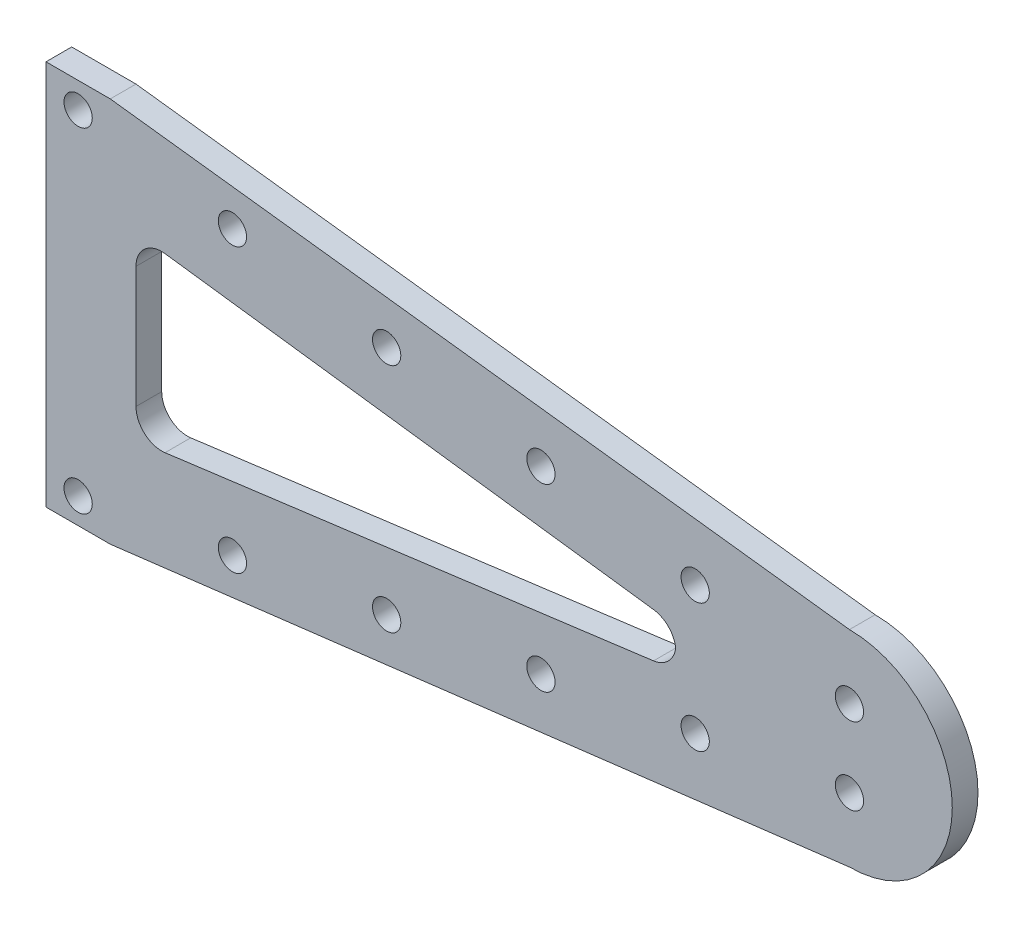
SolidWorks part; units mm, degrees
ref_plane "前基準面" through (0, 0, 0) normal (0, 0, 1) x (1, 0, 0)
ref_plane "上基準面" through (0, 0, 0) normal (0, 1, 0) x (1, 0, 0)
ref_plane "右基準面" through (0, 0, 0) normal (1, 0, 0) x (0, 0, -1)
sketch "草圖1" plane through (0, 0, 0) normal (0, 0, 1) x (1, 0, 0)
  line L0 (2.5, 15) -> (60, 8)
  line L1 (-2.5, 15) -> (2.5, 15)
  line L2 (-2.5, 15) -> (-2.5, -15)
  line L3 (-2.5, -15) -> (2.5, -15)
  line L4 (0, 0) -> (60, 0) construction
  line L5 (-2.5, 15) -> (2.5, -15) construction
  line L6 (-2.5, -15) -> (2.5, 15) construction
  line L7 (2.5, -15) -> (60, -8)
  line L8 (4.5, 0) -> (4.5, 7)
  line L9 (4.5, 7) -> (46.5, 1.5)
  line L10 (46.5, 1.5) -> (46.5, -1.5)
  line L11 (46.5, -1.5) -> (4.5, -7)
  line L12 (4.5, -7) -> (4.5, 0)
  arc A0 (60, -8) -> (60, 8) centre (60, 0) ccw
  circle A1 centre (0, 13) radius 1.1
  circle A2 centre (0, -13) radius 1.1
  circle A3 centre (12, 11) radius 1.1
  circle A4 centre (24, 9) radius 1.1
  circle A5 centre (36, 7) radius 1.1
  circle A6 centre (48, 5) radius 1.1
  circle A7 centre (60, 3) radius 1.1
  circle A8 centre (60, -3) radius 1.1
  circle A9 centre (48, -5) radius 1.1
  circle A10 centre (36, -7) radius 1.1
  circle A11 centre (24, -9) radius 1.1
  circle A12 centre (12, -11) radius 1.1
  point P0 (0, 0)
  dimension "D4" = 16
  dimension "D7" = 2.2
  dimension "D8" = 2.2
  dimension "D1" = 5
  dimension "D2" = 30
  dimension "D3" = 60
  dimension "D5" = 26
  dimension "D6" = 13
  dimension "D9" = 12
  dimension "D10" = 12
  dimension "D11" = 12
  dimension "D12" = 12
  dimension "D13" = 2
  dimension "D14" = 2
  dimension "D15" = 2
  dimension "D16" = 2
  dimension "D17" = 2
  dimension "D18" = 12
  dimension "D19" = 7
  dimension "D20" = 7
  dimension "D21" = 3
  dimension "D22" = 1.5
  dimension "D23" = 42
  dimension "D24" = 4.5
extrude "填料-伸長1" add sketch "草圖1" along normal blind 2
fillet "圓角1" radius 2 4 edges at (46.5, -1.5, 1) (46.5, 1.5, 1) (4.5, -7, 1) (4.5, 7, 1)
